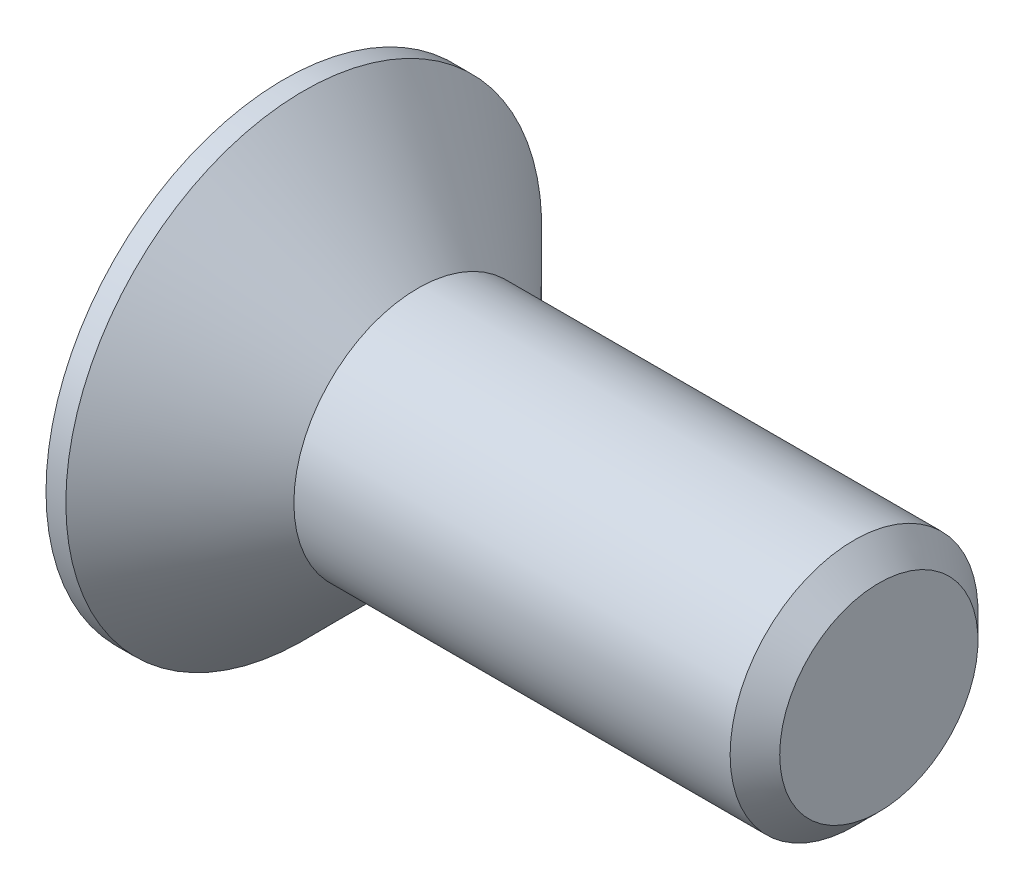
SolidWorks part; units mm, degrees
ref_plane "Front Plane" through (0, 0, 0) normal (0, 0, 1) x (1, 0, 0)
ref_plane "Top Plane" through (0, 0, 0) normal (0, 1, 0) x (1, 0, 0)
ref_plane "Right Plane" through (0, 0, 0) normal (1, 0, 0) x (0, 0, -1)
sketch "Sketch2" plane through (0, 0, 0) normal (0, 0, 1) x (1, 0, 0)
  line L0 (0, 0) -> (0, 2.4)
  line L1 (0, 2.4) -> (0.2, 2.4)
  line L2 (0.2, 2.4) -> (1.35, 1.25)
  line L3 (1.35, 1.25) -> (5.75, 1.25)
  line L4 (5.75, 1.25) -> (6, 1)
  line L5 (6, 1) -> (6, 0)
  line L6 (6, 0) -> (0, 0)
  line L7 (-2.2818, 0) -> (8.0811, 0) construction
  dimension "D1" = 4.8
  dimension "D2" = 0.2
  dimension "D3" = 45
  dimension "D4" = 6
  dimension "D5" = 0.25
  dimension "D6" = 2.5
revolve "Revolve1" add sketch "Sketch2" angle 360 about L7
sketch "Sketch3" plane through (0, 0, 0) normal (-1, 0, 0) x (0, 0, 1)
  line L1 (0.433, -0.75) -> (0.866, 0)
  line L2 (0.866, 0) -> (0.433, 0.75)
  line L3 (0.433, 0.75) -> (-0.433, 0.75)
  line L4 (-0.433, 0.75) -> (-0.866, 0)
  line L5 (-0.866, 0) -> (-0.433, -0.75)
  line L6 (-0.433, -0.75) -> (0.433, -0.75)
  circle A0 centre (0, 0) radius 0.75 construction
  dimension "D1" = 1.5
extrude "Cut-Extrude1" cut sketch "Sketch3" against normal blind 0.8
